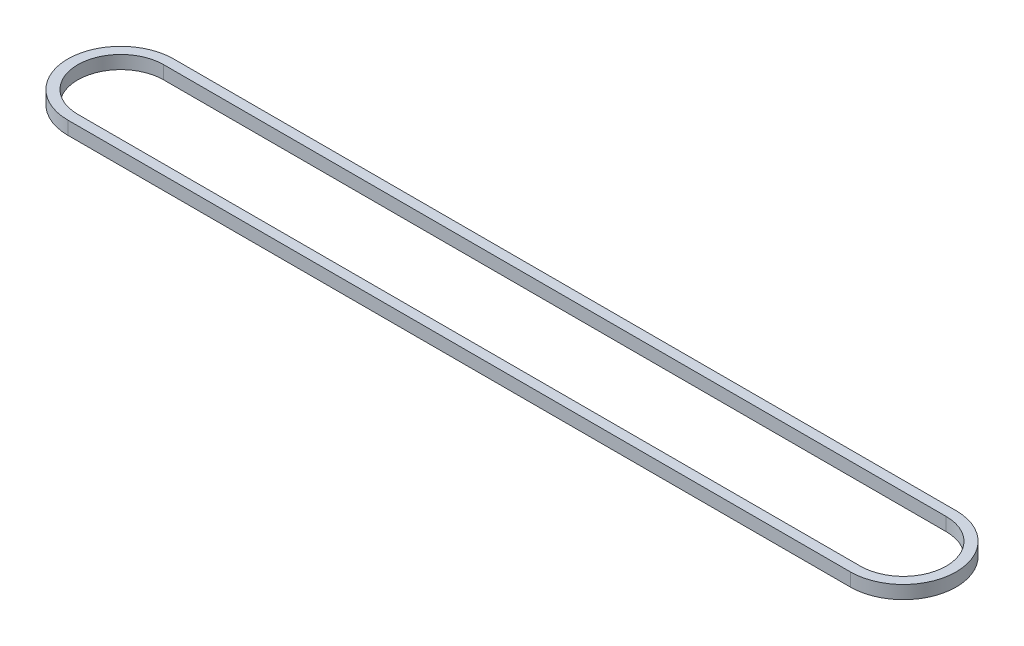
SolidWorks part; units mm, degrees
ref_plane "Front Plane" through (0, 0, 0) normal (0, 0, 1) x (1, 0, 0)
ref_plane "Top Plane" through (0, 0, 0) normal (0, 1, 0) x (1, 0, 0)
ref_plane "Right Plane" through (0, 0, 0) normal (1, 0, 0) x (0, 0, -1)
sketch "Sketch1" plane through (0, 0, 0) normal (0, 1, 0) x (1, 0, 0)
  line L0 (-231.25, 0) -> (231.25, 0) construction
  line L1 (-231.25, 0) -> (231.25, 0) construction
  line L2 (-231.25, 31.287) -> (231.25, 31.287)
  line L3 (-231.25, -31.287) -> (231.25, -31.2869)
  line L4 (-231.25, 0) -> (231.25, 0) construction
  line L5 (-231.25, 25.3941) -> (231.25, 25.3942)
  line L6 (-231.25, -25.3941) -> (231.25, -25.3941)
  line L7 (-231.25, 25.3941) -> (-231.25, 31.287) construction
  arc A0 (-231.25, 31.287) -> (-231.25, -31.287) centre (-231.25, 0) ccw
  arc A1 (231.25, -31.2869) -> (231.25, 31.287) centre (231.25, 0) ccw
  arc A2 (-231.25, 25.3941) -> (-231.25, -25.3941) centre (-231.25, 0) ccw
  arc A3 (231.25, -25.3941) -> (231.25, 25.3942) centre (231.25, 0) ccw
  point P0 (0, 0)
  point P4 (0, 0)
  point P10 (0, 0)
  point P18 (-231.25, 28.3406)
  dimension "D2" = 28.3406
  dimension "D3" = 5.8928
  dimension "D1" = 462.5
extrude "Boss-Extrude1" add sketch "Sketch1" along normal blind 7.7978 contours L3 A1 L2 A0 | L6 A2 L5 A3
